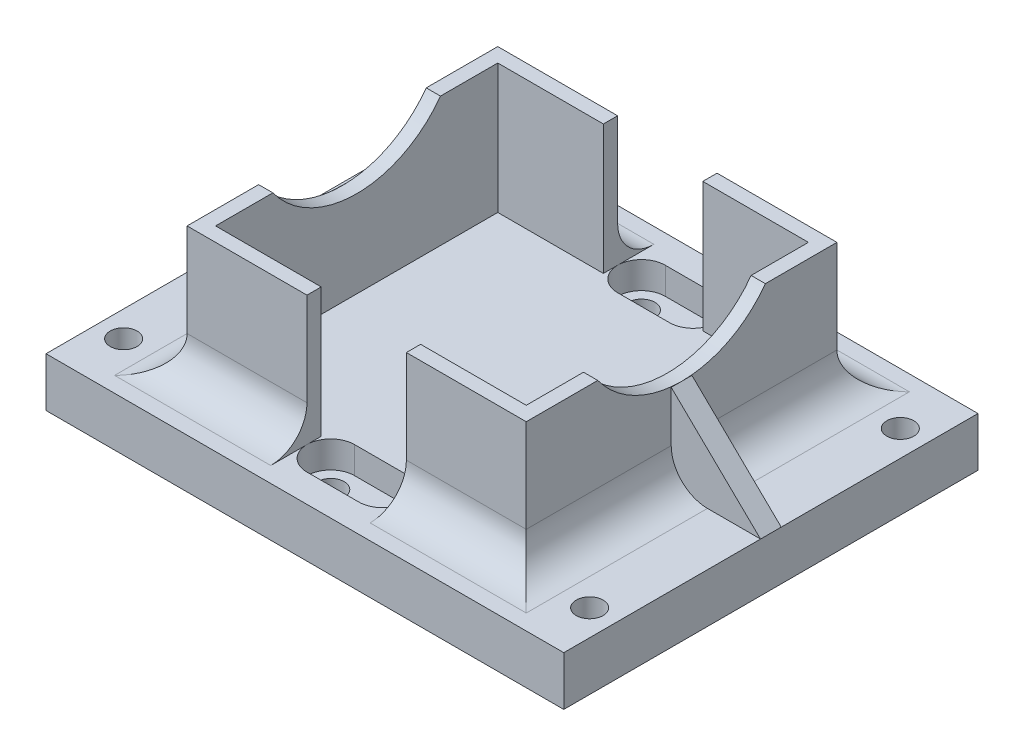
SolidWorks part; units mm, degrees
ref_plane "前视基准面" through (0, 0, 0) normal (0, 0, 1) x (1, 0, 0)
ref_plane "上视基准面" through (0, 0, 0) normal (0, 1, 0) x (1, 0, 0)
ref_plane "右视基准面" through (0, 0, 0) normal (1, 0, 0) x (0, 0, -1)
other "Configuration Table"
sketch "草图1" plane through (0, 0, 0) normal (0, 1, 0) x (1, 0, 0)
  line L0 (-54.1433, 0) -> (63.1838, 0) construction
  line L1 (-50, -40) -> (50, -40)
  line L2 (-50, -40) -> (-50, 40)
  line L3 (-50, 40) -> (50, 40)
  line L4 (50, -40) -> (50, 40)
  line L5 (-50, -40) -> (50, 40) construction
  line L6 (-50, 40) -> (50, -40) construction
  line L7 (0, 47.9487) -> (0, -55.1328) construction
  circle A0 centre (-45, 30) radius 2.6
  circle A1 centre (-5, 30) radius 2.6
  circle A2 centre (-5, -30) radius 2.6
  circle A3 centre (-45, -30) radius 2.6
  circle A4 centre (45, -30) radius 2.6
  circle A5 centre (5, -30) radius 2.6
  circle A6 centre (5, 30) radius 2.6
  circle A7 centre (45, 30) radius 2.6
  point P0 (0, 0)
  point P12 (0, 0)
  dimension "D3" = 5.2
  dimension "D1" = 100
  dimension "D2" = 80
  dimension "D4" = 10
  dimension "D5" = 5
  dimension "D8" = 40
  dimension "D9" = 60
  dimension "D10" = 5
  dimension "D6" = 2
  dimension "D7" = 2
extrude "凸台-拉伸1" add sketch "草图1" along normal blind 9.5
sketch "草图4" plane through (0, 9.5, 0) normal (0, 1, 0) x (1, 0, 0)
  line L4 (0, 42.2525) -> (0, -44.3082) construction
  line L15 (-5, 30) -> (5, 30) construction
  line L16 (-5, 34.6) -> (5, 34.6)
  line L17 (-5, 25.4) -> (5, 25.4)
  line L18 (-5, -30) -> (5, -30) construction
  line L19 (-5, -25.4) -> (5, -25.4)
  line L20 (-5, -34.6) -> (5, -34.6)
  arc A4 (-5, 34.6) -> (-5, 25.4) centre (-5, 30) ccw
  arc A5 (5, 25.4) -> (5, 34.6) centre (5, 30) ccw
  arc A6 (-5, -25.4) -> (-5, -34.6) centre (-5, -30) ccw
  arc A7 (5, -34.6) -> (5, -25.4) centre (5, -30) ccw
  point P35 (0, 30)
  point P40 (0, -30)
  dimension "D4" = 4.6
  dimension "D5" = 4.6
  dimension "D2" = 10
  dimension "D3" = 10
extrude "切除-拉伸1" cut sketch "草图4" against normal blind 5.2
sketch "草图5" plane through (0, 9.5, 0) normal (0, 1, 0) x (1, 0, 0)
  line L0 (-9.6, 30) -> (-9.6, 27.25)
  line L1 (-30, -27.25) -> (30, -27.25)
  line L2 (-30, -27.25) -> (-30, 27.25)
  line L3 (-30, 27.25) -> (30, 27.25)
  line L4 (30, -27.25) -> (30, 27.25)
  line L5 (-30, -27.25) -> (30, 27.25) construction
  line L6 (-30, 27.25) -> (30, -27.25) construction
  line L7 (-9.6, 27.25) -> (-9.6, 30)
  line L8 (9.6, 30) -> (9.6, 27.25)
  line L9 (32.75, -29.9995) -> (-32.75, -29.9995)
  line L10 (32.75, -29.9995) -> (32.75, 29.9995)
  line L11 (32.75, 29.9995) -> (-32.75, 29.9995)
  line L12 (-32.75, -29.9995) -> (-32.75, 29.9995)
  line L13 (32.75, -29.9995) -> (-32.75, 29.9995) construction
  line L14 (32.75, 29.9995) -> (-32.75, -29.9995) construction
  line L15 (-9.6, -30) -> (-9.6, -27.25)
  line L16 (9.6, -30) -> (9.6, -27.25)
  arc A0 (-5, 34.6) -> (-5, 25.4) centre (-5, 30) ccw construction
  arc A1 (5, 25.4) -> (5, 34.6) centre (5, 30) ccw construction
  arc A2 (-5, -25.4) -> (-5, -34.6) centre (-5, -30) ccw construction
  arc A4 (5, -34.6) -> (5, -25.4) centre (5, -30) ccw construction
  point P0 (0, 0)
  point P11 (0, 0)
  dimension "D1" = 60
  dimension "D2" = 54.5
  dimension "D3" = 2.75
  dimension "D4" = 2.7495
extrude "凸台-拉伸2" add sketch "草图5" along normal blind 25 contours L9 L15 L1 L2 L3 L7 L11 L12 | L16 L9 L10 L11 L8 L3 L4 L1 region at (-10.2431, 9.5, -28.6248) region at (21.175, 9.5, -29.3564)
fillet "圆角1" radius 7 6 edges at (-32.75, 9.5, 0) (32.75, 9.5, 0) (21.175, 9.5, 29.9995) (-21.175, 9.5, 29.9995)
sketch "草图7" plane through (-32.75, 0, 0) normal (-1, 0, 0) x (0, 0, 1)
  line L0 (-40, 9.5) -> (40, 9.5) construction
  circle A0 centre (0, 46.25) radius 20
  dimension "D1" = 40
  dimension "D2" = 36.75
extrude "切除-拉伸2" cut sketch "草图7" against normal through all
sketch "草图6" plane through (0, 0, 0) normal (0, 0, 1) x (1, 0, 0)
  line L0 (-32.75, 26.25) -> (-50, 9.5)
  line L1 (-50, 9.5) -> (-32.75, 9.5)
  line L2 (-50, 9.5) -> (50, 9.5) construction
  line L3 (-32.75, 9.5) -> (-32.75, 26.25)
  line L4 (0, 38.4397) -> (0, -19.6976) construction
  line L5 (32.75, 9.5) -> (32.75, 26.25)
  line L6 (50, 9.5) -> (32.75, 9.5)
  line L7 (32.75, 26.25) -> (50, 9.5)
  point P13 (-32.75, 34.5)
  point P14 (-32.75, 26.25)
extrude "凸台-拉伸3" add sketch "草图6" along normal blind 2 and the other way blind 2
